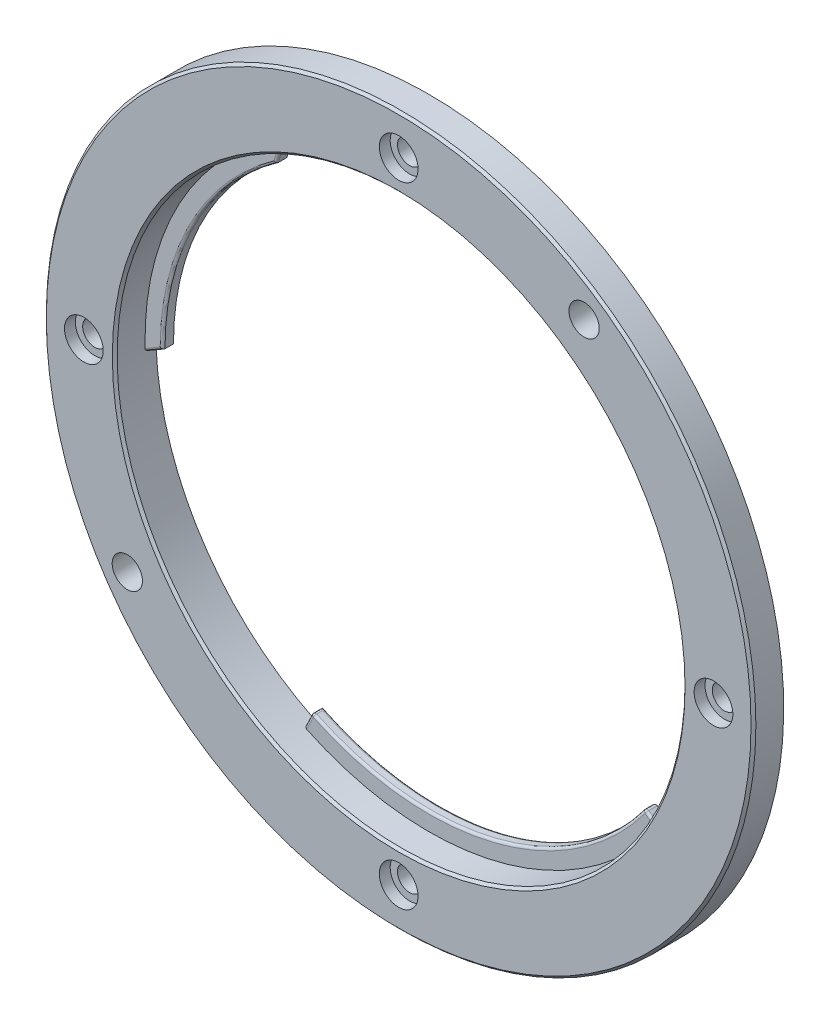
SolidWorks part; units mm, degrees
ref_plane "前视基准面" through (0, 0, 0) normal (0, 0, 1) x (1, 0, 0)
ref_plane "上视基准面" through (0, 0, 0) normal (0, 1, 0) x (1, 0, 0)
ref_plane "右视基准面" through (0, 0, 0) normal (1, 0, 0) x (0, 0, -1)
other "Configuration Table"
sketch "草图1" plane through (0, 0, 0) normal (0, 0, 1) x (1, 0, 0)
  line L0 (0, 0) -> (0, 18.6763) construction
  line L1 (0, 0) -> (17.12, 0) construction
  circle A0 centre (0, 0) radius 23.45
  circle A1 centre (0, 0) radius 29.3
  circle A2 centre (0, 0) radius 26 construction
  circle A3 centre (0, 26) radius 1
  circle A4 centre (-26, 0) radius 1
  circle A5 centre (0, -26) radius 1
  circle A6 centre (26, 0) radius 1
  dimension "D1" = 46.9
  dimension "D2" = 58.6
  dimension "D3" = 52
  dimension "D4" = 2
extrude "凸台-拉伸1" add sketch "草图1" along normal blind 2.5
sketch "草图2" plane through (0, 0, 2.5) normal (0, 0, 1) x (1, 0, 0)
  line L0 (0, 0) -> (-12.8007, 0) construction
  line L1 (0, 0) -> (-22.4107, -14.8333) construction
  line L2 (0, 0) -> (15.311, 22.0871) construction
  circle A0 centre (0, 0) radius 26.875 construction
  circle A1 centre (-22.4107, -14.8333) radius 1.25
  circle A2 centre (15.311, 22.0871) radius 1.25
  dimension "D1" = 53.75
  dimension "D3" = 2.5
  dimension "D4" = 2.5
  dimension "D2" = 33.5
  dimension "D5" = 55.27
extrude "切除-拉伸1" cut sketch "草图2" against normal through all
sketch "草图3" plane through (0, 0, 0) normal (0, 0, -1) x (-1, 0, 0)
  line L0 (50.415, 188.0781) -> (517.0817, 188.0781) construction
  line L1 (0, 0) -> (-18.9714, -13.7836)
  line L2 (0, 0) -> (10.2798, -21.0767)
  line L3 (0, 0) -> (-21.0387, 6.4322) construction
  line L4 (0, 0) -> (-10.6658, 19.2416) construction
  line L5 (0, 0) -> (12.6187, 18.0213) construction
  line L6 (0, 0) -> (22, 0) construction
  line L7 (0, 0) -> (0, -23.45) construction
  line L8 (-21.0387, 6.4322) -> (-22.854, 5.2533)
  line L9 (-10.6658, 19.2416) -> (-9.8901, 21.2624)
  line L10 (12.6187, 18.0213) -> (12.0585, 20.1121)
  line L11 (22, 0) -> (23.4354, -0.8287)
  circle A0 centre (0, 0) radius 23.45
  circle A1 centre (0, 0) radius 23.45 construction
  circle A2 centre (0, 0) radius 22
  circle A3 centre (0, 0) radius 24
  circle M5 centre (0, 0) radius 23.45
  dimension "D1" = 44
  dimension "D12" = 48
  dimension "D2" = 54
  dimension "D3" = 26
  dimension "D4" = 90
  dimension "D5" = 73
  dimension "D6" = 29
  dimension "D7" = 35
  dimension "D8" = 130
  dimension "D9" = 130
  dimension "D10" = 130
  dimension "D11" = 150
extrude "凸台-拉伸2" add sketch "草图3" along normal blind 0.9 contours A2 L9 L8 M5 | A2 L11 L10 M5 | A2 L1 L2 M5 | A3 M5 region at (5.3975, -21.6481, 0) region at (17.1603, 13.8961, 0) region at (-19.7257, 10.2685, 0) region at (23.9321, 0, 0)
fillet "圆角1" radius 0.2 12 edges at (-9.6442, -19.7735, -0.45) (5.3223, -21.3465, -0.9) (17.7984, -12.9313, -0.45) (5.3223, -21.3465, 0) (18.3849, -13.3574, 0) (-9.962, -20.4251, 0) (21.9464, 5.8427, 0) (17.0972, 13.845, 0) (10.278, 20.252, 0) (-22.7177, -0.4144, 0) (-19.5142, 10.1585, 0) (-12.3386, 19.0667, 0)
chamfer "倒角1" distance 0.2 angle 45 2 edges at (29.3, 0, 2.5) (23.45, 0, 2.5)
sketch "草图4" plane through (0, 0, 2.5) normal (0, 0, 1) x (1, 0, 0)
  circle A0 centre (-26, 0) radius 1.6
  circle A1 centre (0, 26) radius 1.6
  circle A2 centre (26, 0) radius 1.6
  circle A3 centre (0, -26) radius 1.6
  dimension "D1" = 3.2
extrude "切除-拉伸2" cut sketch "草图4" against normal blind 0.9
sketch "草图5" plane through (0, 0, 0) normal (0, 0, -1) x (-1, 0, 0)
  line L0 (0, 0) -> (22.4107, -14.8333) construction
  line L1 (21.9411, -9.7257) -> (26.4118, -12.6848)
  line L2 (17.5256, -16.3968) -> (21.9964, -19.3559)
  circle A0 centre (0, 0) radius 24
  circle A1 centre (0, 0) radius 29.3
  circle A2 centre (0, 0) radius 24 construction
  circle A3 centre (0, 0) radius 29.3 construction
  circle A4 centre (22.4107, -14.8333) radius 1.25 construction
  circle A5 centre (22.4107, -14.8333) radius 1.25 construction
  circle M7 centre (0, 0) radius 24
  circle M8 centre (22.4107, -14.8333) radius 1.25
  circle M10 centre (0, 0) radius 29.3
  dimension "D1" = 8
extrude "切除-拉伸3" cut sketch "草图5" against normal blind 0.6 contours L2 L1 M7 M10 M8 region at (-24.1041, -11.3145, 0)
equation "\"2。5\"=10"
